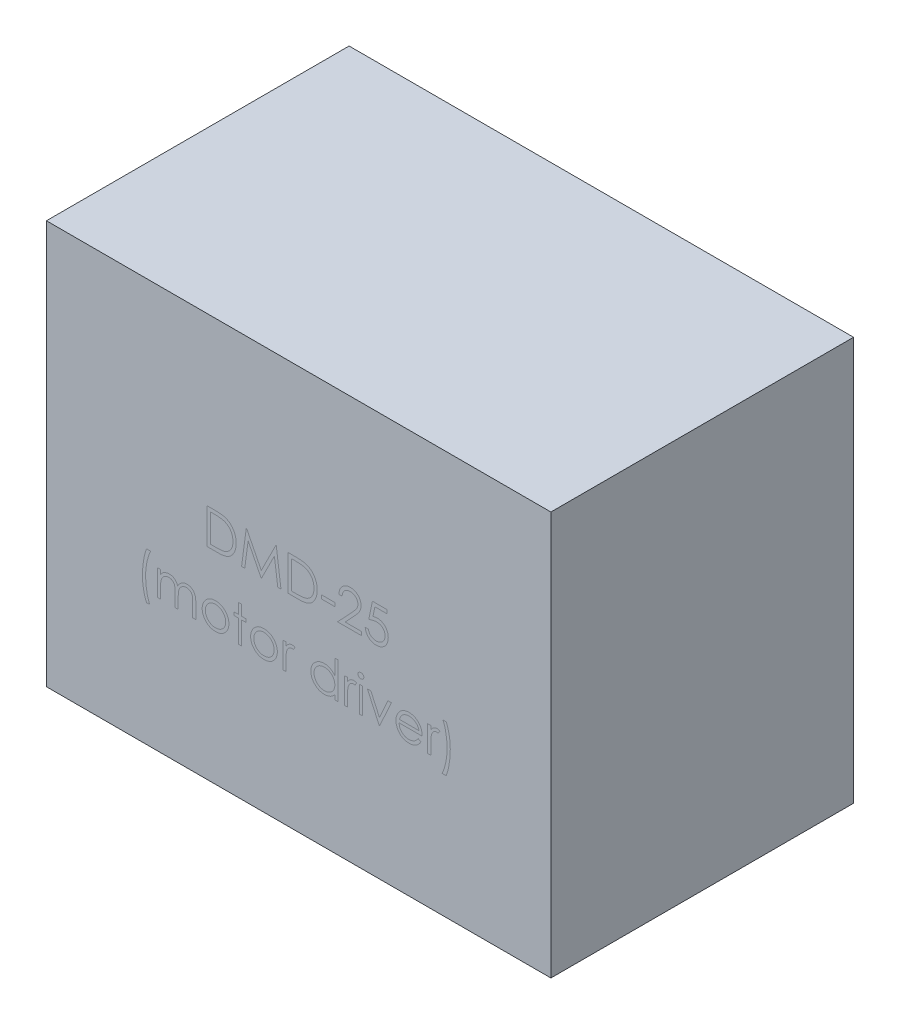
SolidWorks part; units mm, degrees
ref_plane "정면" through (0, 0, 0) normal (0, 0, 1) x (1, 0, 0)
ref_plane "윗면" through (0, 0, 0) normal (0, 1, 0) x (1, 0, 0)
ref_plane "우측면" through (0, 0, 0) normal (1, 0, 0) x (0, 0, -1)
sketch "스케치1" plane through (0, 0, 0) normal (0, 0, 1) x (1, 0, 0)
  line L1 (-25, 20) -> (25, 20)
  line L2 (-25, 20) -> (-25, -20)
  line L3 (-25, -20) -> (25, -20)
  line L4 (25, 20) -> (25, -20)
  line L5 (-25, 20) -> (25, -20) construction
  line L6 (-25, -20) -> (25, 20) construction
  point P0 (0, 0)
  dimension "D1" = 50
  dimension "D2" = 40
extrude "보스-돌출1" add sketch "스케치1" along normal blind 30
ref_plane "평면1" through (0, 0, 40) normal (0, 0, 1) x (1, 0, 0)
sketch "스케치3" plane through (0, 0, 40) normal (0, 0, 1) x (1, 0, 0)
  line L0 (-27.0029, 0) -> (26.5902, 0) construction
  text T0 "DMD-25\r\n(motor driver)"
wrap "곡면 포장1" sketch "스케치3" wrap type scribe source sketch "스케치3" face at (0, 0, 30)
